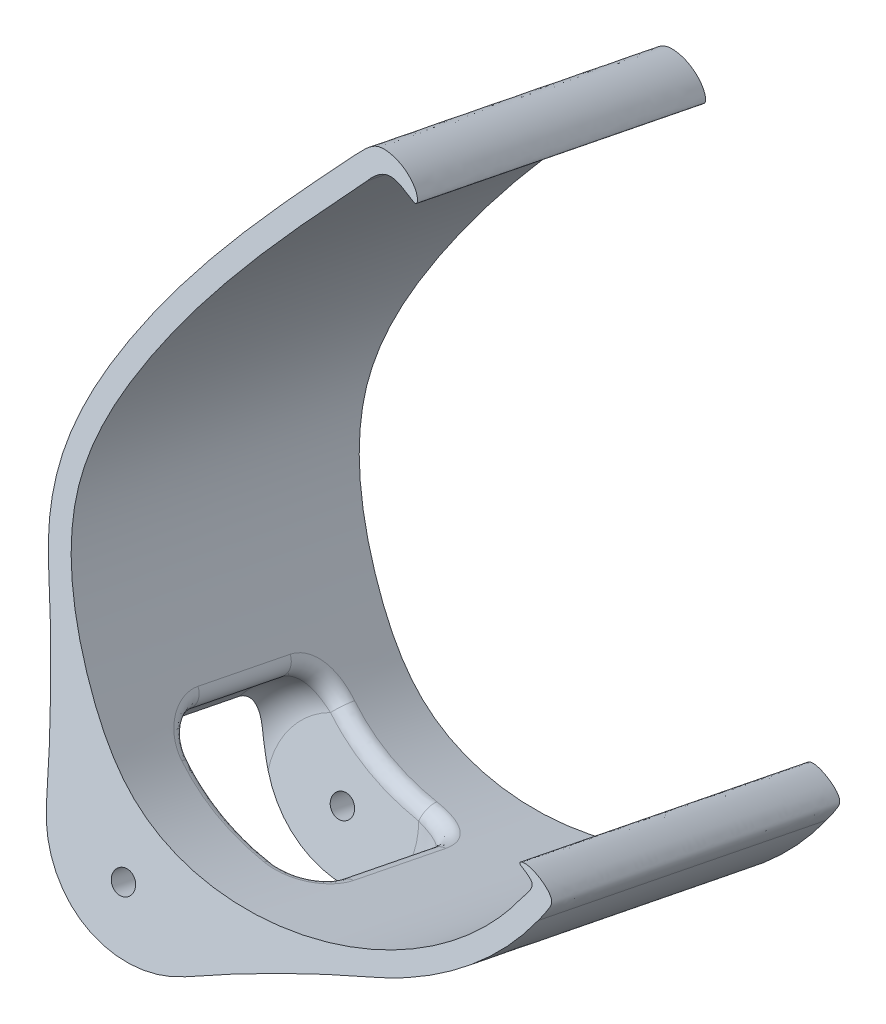
SolidWorks part; units mm, degrees
ref_plane "前视基准面" through (0, 0, 0) normal (0, 0, 1) x (1, 0, 0)
ref_plane "上视基准面" through (0, 0, 0) normal (0, 1, 0) x (1, 0, 0)
ref_plane "右视基准面" through (0, 0, 0) normal (1, 0, 0) x (0, 0, -1)
sketch "草图1" plane through (0, 0, 0) normal (0, 1, 0) x (1, 0, 0)
  line L0 (0, 0) -> (222.6675, 24.1899) construction
ref_axis "基准轴1" through (0, 0, 0) along (0.9942, 0, -0.108)
ref_plane "基准面1" through (0, 0, 0) normal (0.1039, 0.2733, 0.9563) x (0.9942, 0, -0.108)
ref_plane "基准面2" through (-27.5308, -72.4222, -253.4208) normal (0.1039, 0.2733, 0.9563) x (0.9942, 0, -0.108)
ref_plane "基准面3" through (-22.3363, -58.7576, -205.6055) normal (0.1039, 0.2733, 0.9563) x (0.9942, 0, -0.108)
sketch "草图4" plane through (-22.3363, -58.7576, -205.6055) normal (0.1039, 0.2733, 0.9563) x (0.9942, 0, -0.108)
  line L0 (79.159, 272.6491) -> (87.4981, 282.7153) construction
  line L1 (112.1038, 213.2471) -> (114.9313, 217.1192) construction
  line L2 (114.8044, 216.9454) -> (-1.2855, 216.9454) construction
  line L3 (3.7014, 201.9454) -> (89.9835, 201.9454) construction
  line L4 (69.8108, 201.9454) -> (62.7688, 188.7012) construction
  arc A0 (57.0261, 209.791) -> (83.4642, 195.7338) centre (69.8108, 201.9454) ccw
  circle A1 centre (66.2898, 195.3233) radius 1.6
  spline S0 degree 3 poles (74.1484, 285.7795) (62.3556, 270.526) (54.7256, 258.5634) (45.6965, 233.4782) (51.7686, 214.4475) (67.3939, 198.0087) (94.0542, 192.0791) (111.3459, 203.1327) (118.5869, 210.5661) knots 0 0 0 0 0.234318 0.358087 0.509491 0.603672 0.801755 1 1 1 1 construction
  spline S1 degree 3 poles (80.0552, 281.5729) (71.497, 272.1071) (59.1912, 258.4855) (48.9719, 233.6637) (55.5206, 216.4899) (73.5043, 192.358) (106.2983, 197.7848) (115.7948, 213.1989) knots 0 0 0 0 0.26391 0.385656 0.53157 0.620527 1 1 1 1
  spline S2 degree 1 poles (77.8298, 283.5849) (118.349, 211.6253) knots 0 0 1 1 construction
  spline S3 degree 3 poles (77.8298, 283.5849) (75.8007, 281.3406) (71.7472, 276.8567) (65.8259, 269.9344) (60.2485, 262.6426) (56.0502, 256.1061) (53.0427, 250.5139) (51.0295, 246.0767) (49.4577, 241.4254) (48.5035, 236.5677) (48.4264, 231.5459) (49.4505, 225.0235) (51.7915, 218.7893) (54.5436, 213.6893) (56.2872, 210.8596) (58.1323, 208.1682) (60.6616, 205.0473) (64.2833, 201.7266) (68.5241, 199.081) (74.6718, 196.5135) (83.037, 194.9953) (93.3795, 195.638) (103.3044, 198.5934) (110.6119, 202.9332) (115.4578, 207.5231) (117.4748, 210.2064) (118.349, 211.6253) knots 0 0 0 0 0.0625 0.125 0.1875 0.25 0.28125 0.3125 0.34375 0.375 0.40625 0.4375 0.5 0.53125 0.548317 0.563942 0.59375 0.625 0.65625 0.6875 0.75 0.8125 0.875 0.9375 0.96875 1 1 1 1
  spline S4 degree 3 poles (77.8298, 283.5849) (78.616, 284.3547) (79.734, 285.9529) (84.1956, 285.4939) (87.0006, 282.6556) (86.571, 281.0168) (82.6505, 284.5272) (80.4169, 282.0636) (80.0552, 281.5729) knots 0 0 0 0 0.185673 0.241813 0.609549 0.679609 0.872351 1 1 1 1
  spline S5 degree 3 poles (118.349, 211.6253) (118.5722, 211.9225) (119.522, 213.4957) (120.0064, 215.0559) (115.7411, 217.445) (114.2945, 216.719) (117.4065, 215.6444) (116.6878, 214.3479) (115.7948, 213.1989) knots 0 0 0 0 0.111671 0.246985 0.601944 0.662863 0.856176 1 1 1 1
  dimension "D4" = 15
  dimension "D5" = 30
  dimension "D6" = 3.2
  dimension "D2" = 8
  dimension "D3" = 6
  dimension "D1" = 3
extrude "凸台-拉伸1" add sketch "草图4" along normal blind 50 contours S3 A0 | S3 S5 S1 S4 region at (39.5715, 132.6674, -267.0361) region at (23.7178, 180.9146, -279.1018)
fillet "圆角1" radius 200 2 edges
ref_plane "基准面4" through (-18.3885, -48.3726, -169.2659) normal (0.1039, 0.2733, 0.9563) x (0.9946, -0.0285, -0.0999)
sketch "草图6" plane through (-18.3885, -48.3726, -169.2659) normal (0.1039, 0.2733, 0.9563) x (0.9946, -0.0285, -0.0999)
  circle A1 centre (60.4641, 197.2045) radius 15
  dimension "D1" = 30
extrude "切除-拉伸1" cut sketch "草图6" against normal blind 26
fillet "圆角2" radius 5 4 edges at (53.9591, 131.5383, -255.7282) (29.7529, 143.958, -256.6478) (56.6602, 138.6439, -230.8643) (32.454, 151.0636, -231.7838)
fillet "圆角3" radius 2 8 edges at (37.106, 151.4058, -233.7817) (34.7734, 149.4821, -245.1779) (34.3127, 145.6969, -255.5338) (51.8942, 136.1676, -255.4632) (54.8512, 139.1218, -244.3983) (54.9613, 142.2502, -233.8431)
